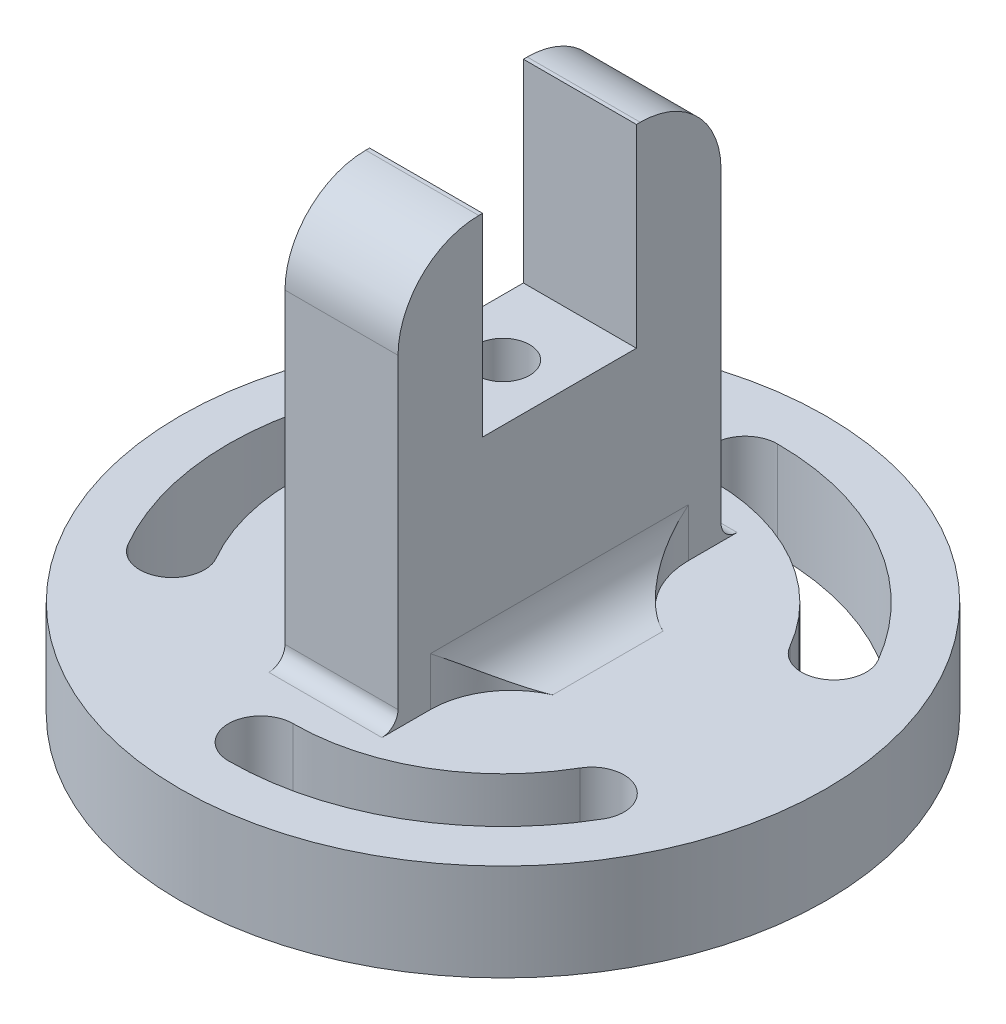
SolidWorks part; units mm, degrees
material "Stainless Steel (ferritic)"
ref_plane "Front Plane" through (0, 0, 0) normal (0, 0, 1) x (1, 0, 0)
ref_plane "Top Plane" through (0, 0, 0) normal (0, 1, 0) x (1, 0, 0)
ref_plane "Right Plane" through (0, 0, 0) normal (1, 0, 0) x (0, 0, -1)
sketch "Sketch1" plane through (0, 0, 0) normal (0, 1, 0) x (1, 0, 0)
  circle A0 centre (0, 0) radius 20
  dimension "D1" = 40
extrude "Boss-Extrude1" add sketch "Sketch1" along normal blind 6
sketch "Sketch2" plane through (0, 6, 0) normal (0, 1, 0) x (1, 0, 0)
  line L0 (0, 0) -> (0, 15) construction
  line L1 (0, 0) -> (12.9904, 7.5) construction
  circle A0 centre (0, 0) radius 15 construction
  arc A1 (0, 17) -> (0, 13) centre (0, 15) ccw
  arc A2 (11.2583, 6.5) -> (14.7224, 8.5) centre (12.9904, 7.5) ccw
  arc A3 (14.7224, 8.5) -> (0, 17) centre (0, 0) ccw
  arc A4 (11.2583, 6.5) -> (0, 13) centre (0, 0) ccw
  dimension "D1" = 30
  dimension "D2" = 4
  dimension "D3" = 60
extrude "Cut-Extrude1" cut sketch "Sketch2" against normal through all
ref_axis "Axis1" through (0, 6, 0) along (0, -1, 0)
pattern_circular "CirPattern1" count 3 over 360 about axis through (0, 6, 0) along (0, -1, 0) of "Cut-Extrude1"
sketch "Sketch3" plane through (0, 6, 0) normal (0, 1, 0) x (1, 0, 0)
  line L0 (-3.5, 10) -> (3.5, -10) construction
  line L1 (-3.5, 10) -> (3.5, 10)
  line L2 (-3.5, 10) -> (-3.5, -10)
  line L3 (-3.5, -10) -> (3.5, -10)
  line L4 (3.5, 10) -> (3.5, -10)
  dimension "D1" = 7
  dimension "D2" = 20
extrude "Boss-Extrude2" add sketch "Sketch3" along normal blind 25
sketch "Sketch4" plane through (3.5, 0, 0) normal (1, 0, 0) x (0, 0, -1)
  line L0 (-10, 31) -> (10, 31) construction
  line L1 (-4.7625, 31) -> (4.7625, 31)
  line L2 (-4.7625, 31) -> (-4.7625, 19)
  line L3 (-4.7625, 19) -> (4.7625, 19)
  line L4 (4.7625, 31) -> (4.7625, 19)
  line L5 (0, 31) -> (0, 51.808) construction
  dimension "D1" = 9.525
  dimension "D2" = 12
extrude "Cut-Extrude2" cut sketch "Sketch4" against normal through all
fillet "Fillet1" radius 1 2 edges at (0, 6, -10) (0, 6, 10)
fillet "Fillet2" radius 3 2 edges at (3.5, 6, 0) (-3.5, 6, 0)
sketch "Sketch5" plane through (0, 6, 0) normal (0, 1, 0) x (1, 0, 0)
  line L0 (-3.5, 10) -> (-3.5, -10) construction
  line L1 (-9.5, 13) -> (-3.5, 13)
  line L2 (-9.5, 13) -> (-9.5, 3)
  line L3 (-9.5, 3) -> (-8.5, 3)
  line L4 (-3.5, 13) -> (-3.5, 8)
  line L5 (-12.6128, 0) -> (14.122, 0) construction
  line L6 (0, 0) -> (0, 14.3646) construction
  line L8 (9.5, 3) -> (8.5, 3)
  line L9 (3.5, 13) -> (3.5, 8)
  line L10 (9.5, 13) -> (3.5, 13)
  line L11 (9.5, 13) -> (9.5, 3)
  line L12 (9.5, -13) -> (9.5, -3)
  line L13 (9.5, -13) -> (3.5, -13)
  line L14 (3.5, -13) -> (3.5, -8)
  line L15 (9.5, -3) -> (8.5, -3)
  line L16 (-3.5, -13) -> (-3.5, -8)
  line L17 (-9.5, -3) -> (-8.5, -3)
  line L18 (-9.5, -13) -> (-9.5, -3)
  line L19 (-9.5, -13) -> (-3.5, -13)
  arc A0 (-3.5, 8) -> (-8.5, 3) centre (-8.5, 8) cw
  arc A1 (3.5, 8) -> (8.5, 3) centre (8.5, 8) ccw
  arc A2 (3.5, -8) -> (8.5, -3) centre (8.5, -8) cw
  arc A3 (-3.5, -8) -> (-8.5, -3) centre (-8.5, -8) ccw
  point P14 (-3.5, 3)
  point P33 (-3.5, -3)
  dimension "D1" = 5
  dimension "D2" = 6
  dimension "D3" = 3
  dimension "D4" = 10
extrude "Cut-Extrude3" cut sketch "Sketch5" along normal through all
hole_wizard "M4x0.7 Tapped Hole1" positions "Sketch7" profile "Sketch6" tap size "M4x0.7" standard "Ansi Metric"
sketch "Sketch7" plane through (0, 19, 0) normal (0, 1, 0) x (-1, 0, 0)
  line L0 (3.5, -4.7625) -> (-3.5, 4.7625) construction
  line L1 (3.5, 4.7625) -> (-3.5, 4.7625) construction
  point P0 (0, 0)
sketch "Sketch6" plane through (0, 19, 0) normal (1, 0, 0) x (0, 0, 1)
  line L0 (0, 0) -> (0, 9.0914)
  line L1 (0, 9.0914) -> (1.65, 8.1)
  line L2 (1.65, 8.1) -> (1.65, 0)
  line L5 (1.65, 0) -> (0, 0)
  line L10 (0, 9.0914) -> (-1.65, 8.1) construction
  line L11 (0, -6.35) -> (0, 107.95) construction
  dimension "Tap Drill Dia." = 3.3
  dimension "Tap Drill Depth" = 8.1
  dimension "Drill Angle" = 118
cosmetic thread "Hole Thread1" parameters "D1"=6, "D2"=4
fillet "Fillet3" radius 5 2 edges at (0, 31, -10) (0, 31, 10)
